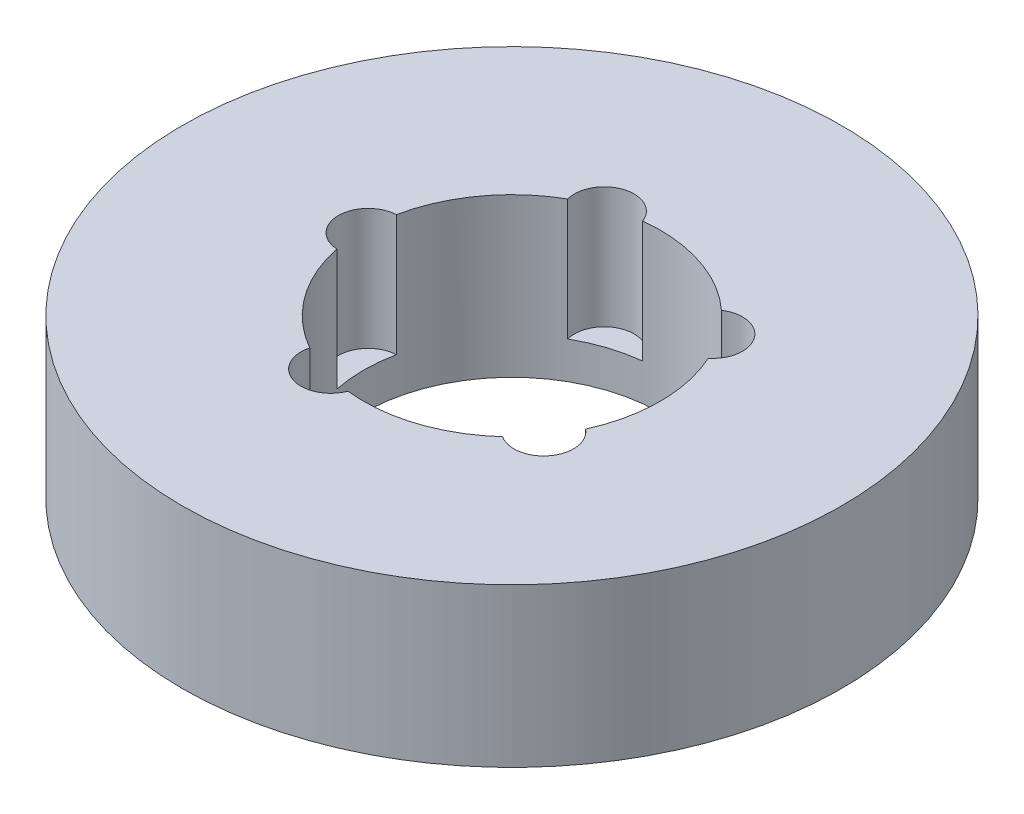
SolidWorks part; units mm, degrees
ref_plane "Front Plane" through (0, 0, 0) normal (0, 0, 1) x (1, 0, 0)
ref_plane "Top Plane" through (0, 0, 0) normal (0, 1, 0) x (1, 0, 0)
ref_plane "Right Plane" through (0, 0, 0) normal (1, 0, 0) x (0, 0, -1)
sketch "Sketch1" plane through (0, 0, 0) normal (0, 1, 0) x (1, 0, 0)
  circle A0 centre (0, 0) radius 50
  dimension "FLANGE_OD" = 100
extrude "Boss-Extrude1" add sketch "Sketch1" along normal blind 24
sketch "Sketch2" plane through (0, 0, 0) normal (0, 1, 0) x (1, 0, 0)
  circle A0 centre (0, 0) radius 22.5
  dimension "BORE_D" = 45
extrude "Cut-Extrude1" cut sketch "Sketch2" along normal through all
sketch "Sketch3" plane through (0, 24, 0) normal (0, 1, 0) x (1, 0, 0)
  circle A0 centre (0, 0) radius 21.8158 construction
  circle A1 centre (-21.8158, 0) radius 4.5196
  dimension "BOLT_D" = 9.0391
  dimension "BOLT_PCD" = 43.6315
extrude "Cut-Extrude2" cut sketch "Sketch3" against normal blind 18.3954
pattern_circular "CirPattern1" count 5 over 360 about axis through (0, 0, 0) along (0, 1, 0) of "Cut-Extrude2"
